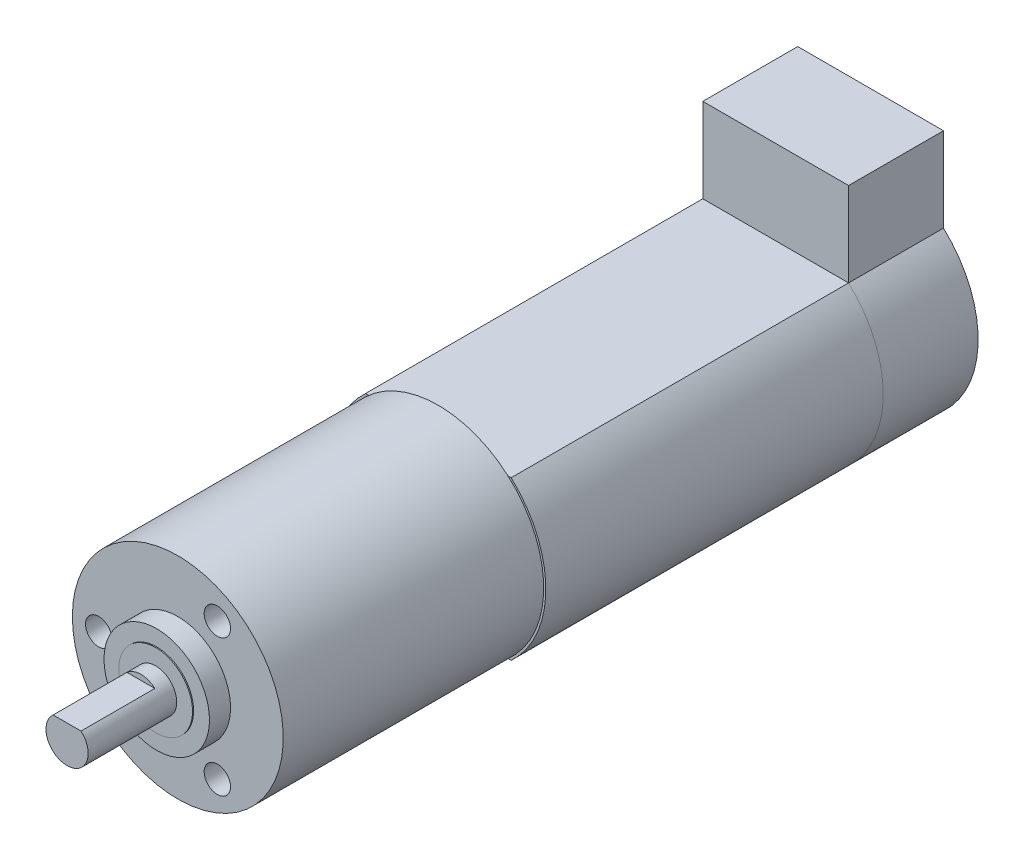
SolidWorks part; units mm, degrees
ref_plane "Front Plane" through (0, 0, 0) normal (0, 0, 1) x (1, 0, 0)
ref_plane "Top Plane" through (0, 0, 0) normal (0, 1, 0) x (1, 0, 0)
ref_plane "Right Plane" through (0, 0, 0) normal (1, 0, 0) x (0, 0, -1)
sketch "Sketch1" plane through (0, 0, 0) normal (0, 0, 1) x (1, 0, 0)
  line L0 (-1.3229, 1.5) -> (1.3229, 1.5)
  arc A0 (-1.3229, 1.5) -> (1.3229, 1.5) centre (0, 0) ccw
  dimension "D1" = 2
  dimension "D2" = 1.5
extrude "Boss-Extrude1" add sketch "Sketch1" against normal blind 7
sketch "Sketch2" plane through (0, 0, -7) normal (0, 0, -1) x (-1, 0, 0)
  circle A0 centre (0, 0) radius 2
extrude "Boss-Extrude2" add sketch "Sketch2" along normal blind 1.4
sketch "Sketch3" plane through (0, 0, -8.4) normal (0, 0, -1) x (-1, 0, 0)
  circle A0 centre (0, 0) radius 3.5
  dimension "D1" = 7
extrude "Boss-Extrude3" add sketch "Sketch3" along normal blind 0.1
sketch "Sketch4" plane through (0, 0, -8.5) normal (0, 0, -1) x (-1, 0, 0)
  circle A0 centre (0, 0) radius 5
  dimension "D1" = 10
extrude "Boss-Extrude4" add sketch "Sketch4" along normal blind 2 separate body
sketch "Sketch5" plane through (0, 0, -10.5) normal (0, 0, -1) x (-1, 0, 0)
  circle A0 centre (0, 0) radius 10
  dimension "D1" = 20
extrude "Boss-Extrude5" add sketch "Sketch5" along normal blind 24.7
sketch "Sketch6" plane through (0, 0, -10.5) normal (0, 0, 1) x (1, 0, 0)
  line L0 (0, 0) -> (3.75, 6.4952) construction
  line L1 (3.75, -6.4952) -> (0, 0) construction
  line L2 (0, 0) -> (-7.5, 0) construction
  line L3 (0, 0) -> (0, 10) construction
  circle A0 centre (0, 0) radius 7.5 construction
  circle A1 centre (3.75, 6.4952) radius 1.25
  circle A2 centre (3.75, -6.4952) radius 1.25
  circle A3 centre (-7.5, 0) radius 1.25
  circle A4 centre (0, 0) radius 10 construction
  dimension "D1" = 15
  dimension "D5" = 2.5
  dimension "D2" = 120
  dimension "D3" = 120
  dimension "D4" = 30
extrude "Screw Holes" cut sketch "Sketch6" against normal blind 5
sketch "Sketch10" plane through (0, 0, -35.2) normal (0, 0, -1) x (-1, 0, 0)
  line L0 (-6.913, 7.5) -> (6.913, 7.5)
  line L1 (-6.913, -7.5) -> (6.913, -7.5)
  arc A0 (-6.913, 7.5) -> (-6.913, -7.5) centre (0, 0) ccw
  arc A1 (6.913, -7.5) -> (6.913, 7.5) centre (0, 0) ccw
  point P7 (0, 0)
  dimension "D1" = 10.2
  dimension "D2" = 15
extrude "Motor" add sketch "Sketch10" along normal blind 32 separate body
sketch "Sketch11" plane through (0, 0, -67.2) normal (0, 0, -1) x (-1, 0, 0)
  line L1 (-6.913, -7.5) -> (6.913, -7.5)
  line L4 (-6.913, 7.5) -> (-6.913, 15.5)
  line L5 (-6.913, 15.5) -> (6.913, 15.5)
  line L6 (6.913, 7.5) -> (6.913, 15.5)
  arc A0 (6.913, -7.5) -> (6.913, 7.5) centre (0, 0) ccw
  arc A1 (-6.913, 7.5) -> (-6.913, -7.5) centre (0, 0) ccw
  dimension "D1" = 23
extrude "Encoder" add sketch "Sketch11" along normal blind 9 separate body
